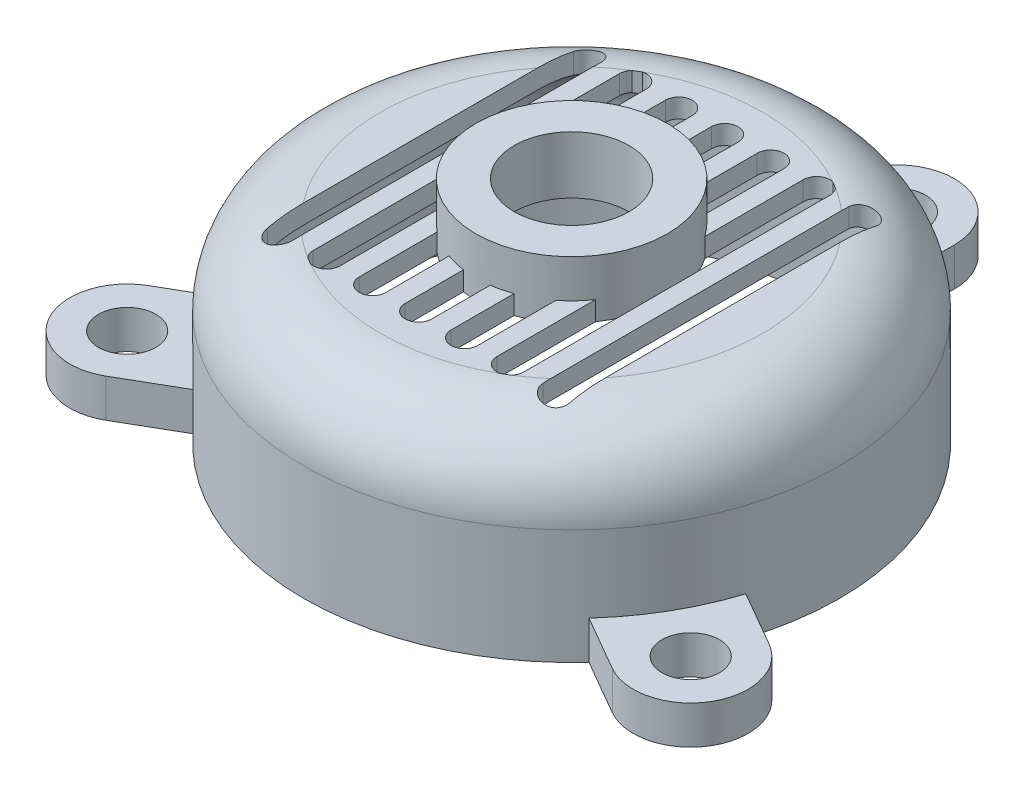
SolidWorks part; units mm, degrees
material "6061 Alloy"
ref_plane "Front Plane" through (0, 0, 0) normal (0, 0, 1) x (1, 0, 0)
ref_plane "Top Plane" through (0, 0, 0) normal (0, 1, 0) x (1, 0, 0)
ref_plane "Right Plane" through (0, 0, 0) normal (1, 0, 0) x (0, 0, -1)
sketch "Sketch1" plane through (0, 0, 0) normal (1, 0, 0) x (0, 0, -1)
  line L0 (-131.8742, 0) -> (131.8742, 0) construction
  line L1 (0, -95.4531) -> (0, 95.4531) construction
  line L2 (0, 63.5) -> (63.5, 63.5)
  line L3 (88.9, 38.1) -> (88.9, 0)
  line L4 (0, 57.15) -> (63.5, 57.15)
  line L5 (82.55, 38.1) -> (82.55, 0)
  line L6 (82.55, 0) -> (88.9, 0)
  line L7 (0, 63.5) -> (0, 57.15)
  line L8 (0, 63.5) -> (0, 57.15)
  arc A0 (88.9, 38.1) -> (63.5, 63.5) centre (63.5, 38.1) ccw
  arc A1 (82.55, 38.1) -> (63.5, 57.15) centre (63.5, 38.1) ccw
  point P4 (0, 0)
  point P8 (0, 0)
  point P13 (88.9, 63.5)
  dimension "D3" = 25.4
  dimension "D1" = 63.5
  dimension "D2" = 88.9
  dimension "D4" = 6.35
revolve "Revolve1" add sketch "Sketch1" angle 360 about L1 region at (0, 62.4075, -31.75)
sketch "Sketch2" plane through (0, 0, 0) normal (0, 1, 0) x (1, 0, 0)
  line L0 (0, -106.402) -> (0, 106.402) construction
  line L1 (-19.05, 107.95) -> (-19.05, 86.8349)
  line L2 (19.05, 107.95) -> (19.05, 86.8349)
  line L3 (103.0124, -37.4772) -> (84.7263, -26.9197)
  line L4 (83.9624, -70.4728) -> (65.6763, -59.9153)
  line L5 (-83.9624, -70.4728) -> (-65.6763, -59.9153)
  line L6 (-103.0124, -37.4772) -> (-84.7263, -26.9197)
  arc A0 (19.05, 107.95) -> (-19.05, 107.95) centre (0, 107.95) ccw
  arc A1 (83.9624, -70.4728) -> (103.0124, -37.4772) centre (93.4874, -53.975) ccw
  arc A2 (-103.0124, -37.4772) -> (-83.9624, -70.4728) centre (-93.4874, -53.975) ccw
  circle A3 centre (0, 0) radius 88.9
  arc A4 (-84.7263, -26.9197) -> (-65.6763, -59.9153) centre (0, 0) ccw
  arc A5 (19.05, 86.8349) -> (-19.05, 86.8349) centre (0, 0) ccw
  arc A6 (65.6763, -59.9153) -> (84.7263, -26.9197) centre (0, 0) ccw
  circle A8 centre (0, 107.95) radius 9.525
  circle A9 centre (93.4874, -53.975) radius 9.525
  circle A10 centre (-93.4874, -53.975) radius 9.525
  point P4 (0, 0)
  point P25 (0, 0)
  point P29 (0, 0)
  dimension "D1" = 38.1
  dimension "D5" = 19.05
  dimension "D2" = 107.95
  dimension "D6" = 3
  dimension "D3" = 0
  dimension "D4" = 3
extrude "Boss-Extrude1" add sketch "Sketch2" along normal blind 12.7
sketch "Sketch3" plane through (0, 63.5, 0) normal (0, 1, 0) x (1, 0, 0)
  line L0 (-134.2624, 0) -> (134.2624, 0) construction
  line L1 (0, -131.0312) -> (0, 131.0312) construction
  line L2 (0, 50.8) -> (0, -50.8) construction
  line L3 (4.445, 50.8) -> (4.445, -50.8)
  line L4 (-4.445, 50.8) -> (-4.445, -50.8)
  line L5 (15.24, 50.8) -> (15.24, -50.8) construction
  line L6 (19.685, 50.8) -> (19.685, -50.8)
  line L7 (10.795, 50.8) -> (10.795, -50.8)
  line L8 (30.48, 50.8) -> (30.48, -50.8) construction
  line L9 (34.925, 50.8) -> (34.925, -50.8)
  line L10 (26.035, 50.8) -> (26.035, -50.8)
  line L11 (45.72, 50.8) -> (45.72, -50.8) construction
  line L12 (50.165, 50.8) -> (50.165, -50.8)
  line L13 (41.275, 50.8) -> (41.275, -50.8)
  line L14 (0, 50.8) -> (0, -50.8) construction
  line L15 (4.445, 50.8) -> (4.445, -50.8)
  line L16 (-4.445, 50.8) -> (-4.445, -50.8)
  line L17 (15.24, 50.8) -> (15.24, -50.8) construction
  line L18 (19.685, 50.8) -> (19.685, -50.8)
  line L19 (10.795, 50.8) -> (10.795, -50.8)
  line L20 (30.48, 50.8) -> (30.48, -50.8) construction
  line L21 (34.925, 50.8) -> (34.925, -50.8)
  line L22 (26.035, 50.8) -> (26.035, -50.8)
  line L23 (-15.24, 50.8) -> (-15.24, -50.8) construction
  line L24 (-10.795, 50.8) -> (-10.795, -50.8)
  line L25 (-19.685, 50.8) -> (-19.685, -50.8)
  line L26 (0, 50.8) -> (0, -50.8) construction
  line L27 (4.445, 50.8) -> (4.445, -50.8)
  line L28 (-4.445, 50.8) -> (-4.445, -50.8)
  line L29 (15.24, 50.8) -> (15.24, -50.8) construction
  line L30 (19.685, 50.8) -> (19.685, -50.8)
  line L31 (10.795, 50.8) -> (10.795, -50.8)
  line L32 (-30.48, 50.8) -> (-30.48, -50.8) construction
  line L33 (-26.035, 50.8) -> (-26.035, -50.8)
  line L34 (-34.925, 50.8) -> (-34.925, -50.8)
  line L35 (-15.24, 50.8) -> (-15.24, -50.8) construction
  line L36 (-10.795, 50.8) -> (-10.795, -50.8)
  line L37 (-19.685, 50.8) -> (-19.685, -50.8)
  line L38 (0, 50.8) -> (0, -50.8) construction
  line L39 (4.445, 50.8) -> (4.445, -50.8)
  line L40 (-4.445, 50.8) -> (-4.445, -50.8)
  line L41 (-15.24, 50.8) -> (-15.24, -50.8) construction
  line L42 (-10.795, 50.8) -> (-10.795, -50.8)
  line L43 (-19.685, 50.8) -> (-19.685, -50.8)
  line L44 (-30.48, 50.8) -> (-30.48, -50.8) construction
  line L45 (-26.035, 50.8) -> (-26.035, -50.8)
  line L46 (-34.925, 50.8) -> (-34.925, -50.8)
  line L47 (-45.72, 50.8) -> (-45.72, -50.8) construction
  line L48 (-41.275, 50.8) -> (-41.275, -50.8)
  line L49 (-50.165, 50.8) -> (-50.165, -50.8)
  arc A0 (4.445, 50.8) -> (-4.445, 50.8) centre (0, 50.8) ccw
  arc A1 (-4.445, -50.8) -> (4.445, -50.8) centre (0, -50.8) ccw
  arc A2 (19.685, 50.8) -> (10.795, 50.8) centre (15.24, 50.8) ccw
  arc A3 (10.795, -50.8) -> (19.685, -50.8) centre (15.24, -50.8) ccw
  arc A4 (34.925, 50.8) -> (26.035, 50.8) centre (30.48, 50.8) ccw
  arc A5 (26.035, -50.8) -> (34.925, -50.8) centre (30.48, -50.8) ccw
  arc A6 (50.165, 50.8) -> (41.275, 50.8) centre (45.72, 50.8) ccw
  arc A7 (41.275, -50.8) -> (50.165, -50.8) centre (45.72, -50.8) ccw
  arc A8 (4.445, 50.8) -> (-4.445, 50.8) centre (0, 50.8) ccw
  arc A9 (-4.445, -50.8) -> (4.445, -50.8) centre (0, -50.8) ccw
  arc A10 (19.685, 50.8) -> (10.795, 50.8) centre (15.24, 50.8) ccw
  arc A11 (10.795, -50.8) -> (19.685, -50.8) centre (15.24, -50.8) ccw
  arc A12 (34.925, 50.8) -> (26.035, 50.8) centre (30.48, 50.8) ccw
  arc A13 (26.035, -50.8) -> (34.925, -50.8) centre (30.48, -50.8) ccw
  arc A14 (-10.795, 50.8) -> (-19.685, 50.8) centre (-15.24, 50.8) ccw
  arc A15 (-19.685, -50.8) -> (-10.795, -50.8) centre (-15.24, -50.8) ccw
  arc A16 (4.445, 50.8) -> (-4.445, 50.8) centre (0, 50.8) ccw
  arc A17 (-4.445, -50.8) -> (4.445, -50.8) centre (0, -50.8) ccw
  arc A18 (19.685, 50.8) -> (10.795, 50.8) centre (15.24, 50.8) ccw
  arc A19 (10.795, -50.8) -> (19.685, -50.8) centre (15.24, -50.8) ccw
  arc A20 (-26.035, 50.8) -> (-34.925, 50.8) centre (-30.48, 50.8) ccw
  arc A21 (-34.925, -50.8) -> (-26.035, -50.8) centre (-30.48, -50.8) ccw
  arc A22 (-10.795, 50.8) -> (-19.685, 50.8) centre (-15.24, 50.8) ccw
  arc A23 (-19.685, -50.8) -> (-10.795, -50.8) centre (-15.24, -50.8) ccw
  arc A24 (4.445, 50.8) -> (-4.445, 50.8) centre (0, 50.8) ccw
  arc A25 (-4.445, -50.8) -> (4.445, -50.8) centre (0, -50.8) ccw
  arc A26 (-10.795, 50.8) -> (-19.685, 50.8) centre (-15.24, 50.8) ccw
  arc A27 (-19.685, -50.8) -> (-10.795, -50.8) centre (-15.24, -50.8) ccw
  arc A28 (-26.035, 50.8) -> (-34.925, 50.8) centre (-30.48, 50.8) ccw
  arc A29 (-34.925, -50.8) -> (-26.035, -50.8) centre (-30.48, -50.8) ccw
  arc A30 (-41.275, 50.8) -> (-50.165, 50.8) centre (-45.72, 50.8) ccw
  arc A31 (-50.165, -50.8) -> (-41.275, -50.8) centre (-45.72, -50.8) ccw
  point P5 (0, 0)
  point P9 (0, 0)
  point P11 (0, 0)
  point P21 (15.24, 0)
  point P28 (30.48, 0)
  point P35 (45.72, 0)
  point P42 (0, 0)
  point P49 (15.24, 0)
  point P56 (30.48, 0)
  point P63 (-15.24, 0)
  point P70 (0, 0)
  point P77 (15.24, 0)
  point P84 (-30.48, 0)
  point P91 (-15.24, 0)
  point P98 (0, 0)
  point P105 (-15.24, 0)
  point P112 (-30.48, 0)
  point P119 (-45.72, 0)
  circle M4 centre (0, 0) radius 63.5
  dimension "D1" = 0
  dimension "D2" = 8.89
  dimension "D3" = 101.6
  dimension "D6" = 45.72
  dimension "D4" = 4
  dimension "D5" = 4
extrude "Cut-Extrude1" cut sketch "Sketch3" against normal through all contours L48 A30 L49 M4 | L49 A31 L48 M4 | L49 L48 M4 | L34 A21 L33 A20 M4 | L25 A15 L24 A14 | L4 A1 L3 A0 | L7 A3 L6 A2 | A5 L9 A4 L10 M4 | L12 A6 L13 M4 | L13 L12 M4 | L13 A7 L12 M4 region at (0, 63.5, 0) region at (15.24, 63.5, 0) region at (30.4785, 63.5, 0) region at (45.5634, 63.5, 0) region at (46.3825, 63.5, -48.8014) region at (46.3825, 63.5, 48.8014) region at (-30.4785, 63.5, 0) region at (-46.3825, 63.5, -48.8014) region at (-45.5634, 63.5, 0) region at (-46.3825, 63.5, 48.8014) region at (-15.24, 63.5, 0)
sketch "Sketch5" plane through (0, 63.5, 0) normal (0, 1, 0) x (1, 0, 0)
  circle A0 centre (0, 0) radius 31.75
  dimension "D1" = 63.5
extrude "Boss-Extrude2" add sketch "Sketch5" along normal blind 19.05 from offset 6.35 offset against normal yes
sketch "Sketch6" plane through (0, 76.2, 0) normal (0, 1, 0) x (1, 0, 0)
  circle A0 centre (0, 0) radius 19.05
  dimension "D1" = 38.1
extrude "Cut-Extrude2" cut sketch "Sketch6" against normal through all
